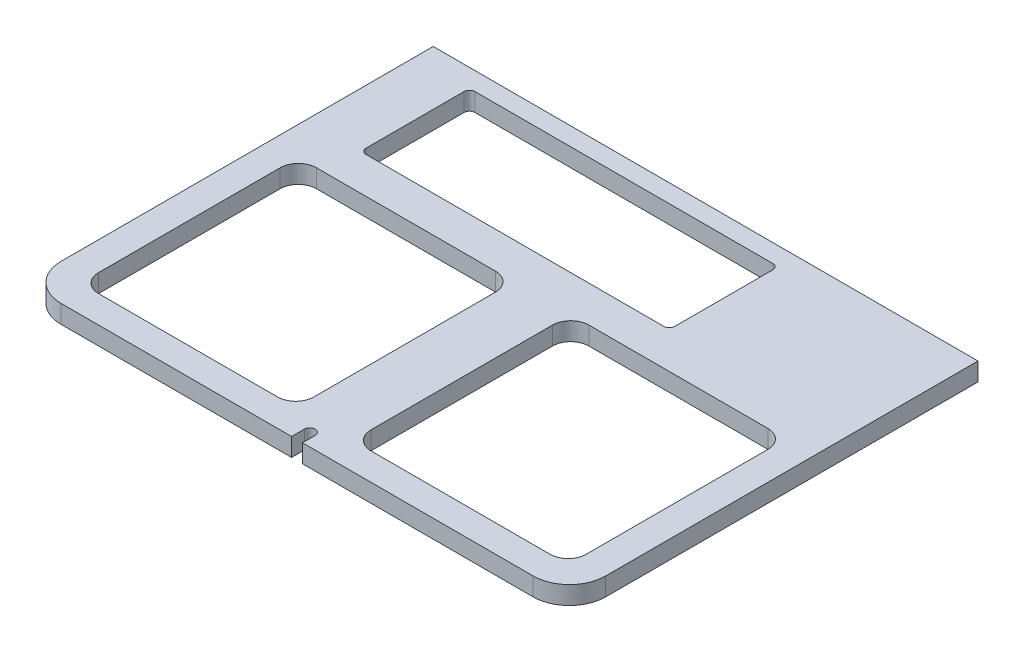
SolidWorks part; units mm, degrees
ref_plane "Ebene vorne" through (0, 0, 0) normal (0, 0, 1) x (1, 0, 0)
ref_plane "Ebene oben" through (0, 0, 0) normal (0, 1, 0) x (1, 0, 0)
ref_plane "Ebene rechts" through (0, 0, 0) normal (1, 0, 0) x (0, 0, -1)
sketch "Skizze1" plane through (0, 10, 0) normal (0, 1, 0) x (1, 0, 0)
  line L0 (0, -75) -> (130, -75)
  line L2 (0, -75) -> (0, 75.7029)
  line L3 (0, 75.7029) -> (150, 75.7029) construction
  line L4 (150, -55) -> (150, 75.7029)
  line L5 (150, -55) -> (150, 150) construction
  line L6 (15.7029, -60) -> (15.7029, -75.7029) construction
  line L7 (15.7029, 60) -> (134.2971, 60)
  line L8 (15.7029, 60) -> (15.7029, -60)
  line L9 (15.7029, -60) -> (134.2971, -60)
  line L10 (134.2971, 60) -> (134.2971, -60)
  line L11 (15.7029, -75.7029) -> (15.7029, -60) construction
  line L12 (0, -60) -> (15.7029, -60) construction
  line L13 (134.2971, 60) -> (134.2971, 75.7029) construction
  line L14 (134.2971, 60) -> (150, 60) construction
  line L15 (150, 75.7029) -> (150, 150)
  line L16 (150, 150) -> (0, 150)
  line L17 (0, 150) -> (0, 75.7029)
  arc A0 (130, -75) -> (150, -55) centre (130, -55) ccw
  arc A1 (130, -75) -> (150, -55) centre (130, -55) ccw construction
  dimension "D1" = 120
extrude "Linear austragen1" add sketch "Skizze1" along normal blind 10
fillet "Verrundung2" radius 10 4 edges at (15.7029, 15, 60) (134.2971, 15, 60) (134.2971, 15, -60) (15.7029, 15, -60)
mirror "Spiegeln1" about plane through (0, 20, -150) normal (1, 0, 0) of "Verrundung2", "Linear austragen1"
sketch "Skizze3" plane through (0, 10, 0) normal (0, -1, 0) x (1, 0, 0)
  line L0 (-150, 55) -> (-150, -150) construction
  line L1 (-120, -80) -> (50, -80)
  line L2 (-120, -80) -> (-120, -140)
  line L3 (-120, -140) -> (50, -140)
  line L4 (50, -80) -> (50, -140)
  line L5 (150, -150) -> (-150, -150) construction
  line L6 (0, -60.4164) -> (0, -150) construction
  dimension "D1" = 30
  dimension "D2" = 10
  dimension "D3" = 50
  dimension "D4" = 60
extrude "Schnitt-Linear austragen1" cut sketch "Skizze3" against normal blind 10
fillet "Verrundung3" radius 3 4 edges at (-120, 15, -140) (50, 15, -140) (50, 15, -80) (-120, 15, -80)
sketch "Skizze4" plane through (0, 10, 0) normal (0, -1, 0) x (1, 0, 0)
  line L0 (-3.0001, 75) -> (-3.0001, 68)
  line L1 (-130, 75) -> (130, 75) construction
  line L2 (-3.0001, 75) -> (2.9592, 75)
  line L3 (2.9592, 75) -> (2.9999, 68.0175)
  arc A0 (-3.0001, 68) -> (2.9999, 68.0175) centre (-0.0001, 68) ccw
  dimension "D2" = 3
  dimension "D1" = 7
extrude "Schnitt-Linear austragen2" cut sketch "Skizze4" against normal blind 10
